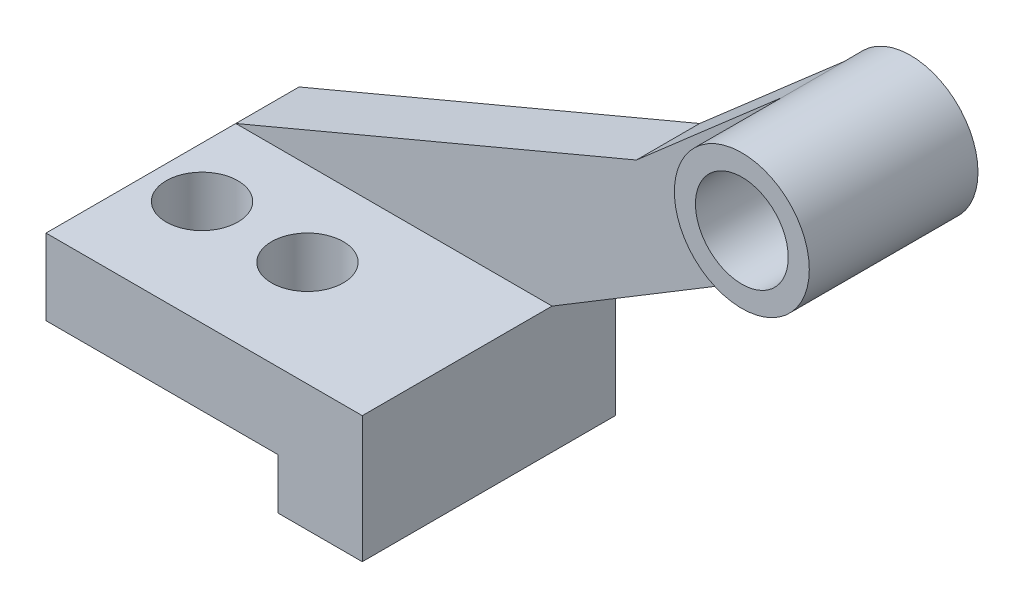
SolidWorks part; units mm, degrees
ref_plane "Front Plane" through (0, 0, 0) normal (0, 0, 1) x (1, 0, 0)
ref_plane "Top Plane" through (0, 0, 0) normal (0, 1, 0) x (1, 0, 0)
ref_plane "Right Plane" through (0, 0, 0) normal (1, 0, 0) x (0, 0, -1)
sketch "Sketch1" plane through (0, 0, 0) normal (0, 0, 1) x (1, 0, 0)
  line L1 (-62.732, -36.1084) -> (-7.732, -36.1084)
  line L2 (-7.732, -36.1084) -> (-7.732, -48.1084)
  line L3 (-7.732, -48.1084) -> (12.268, -48.1084)
  line L4 (12.268, -48.1084) -> (12.268, -18.1084)
  line L5 (12.268, -18.1084) -> (-62.732, -18.1084)
  line L12 (-62.732, -18.1084) -> (-62.732, -36.1084)
  line L13 (32.268, 21.8916) -> (66.7547, 51.9526)
  line L14 (32.268, 21.8916) -> (-62.732, -18.1084)
  line L15 (12.268, -18.1084) -> (85.5468, 26.1999)
  circle A0 centre (77.268, 39.8915) radius 16
  circle A1 centre (77.268, 39.8915) radius 11
extrude "Boss-Extrude1" add sketch "Sketch1" along normal blind 60 contours L5 L12 L1 L2 L3 L4 region at (-21.081, -29.3726, 0)
extrude "Boss-Extrude2" add sketch "Sketch1<3>" along normal blind 15 contours A0 L13 L14 L5 L15 region at (18.8377, 5.0493, 0)
sketch "Sketch1<3>" plane through (0, 0, 0) normal (0, 0, 1) x (1, 0, 0) same geometry as "Sketch1"
extrude "Boss-Extrude3" add sketch "Sketch1<4>" along normal blind 35 and the other way blind 5 contours A0 A1 region at (64.7088, 30.727, 0)
sketch "Sketch1<4>" plane through (0, 0, 0) normal (0, 0, 1) x (1, 0, 0) same geometry as "Sketch1"
sketch "Sketch2" plane through (0, -18.1084, 0) normal (0, 1, 0) x (1, 0, 0)
  line L0 (-62.732, -60) -> (-62.732, -15) construction
  line L1 (12.268, -60) -> (-62.732, -60) construction
  circle A0 centre (-50.732, -35) radius 8.5
  circle A1 centre (-25.732, -35) radius 8.5
  dimension "D1" = 17
  dimension "D4" = 25
  dimension "D6" = 17
  dimension "D2" = 12
  dimension "D3" = 25
  dimension "D5" = 0
extrude "Cut-Extrude1" cut sketch "Sketch2" against normal blind 35 contours A0 | A1
